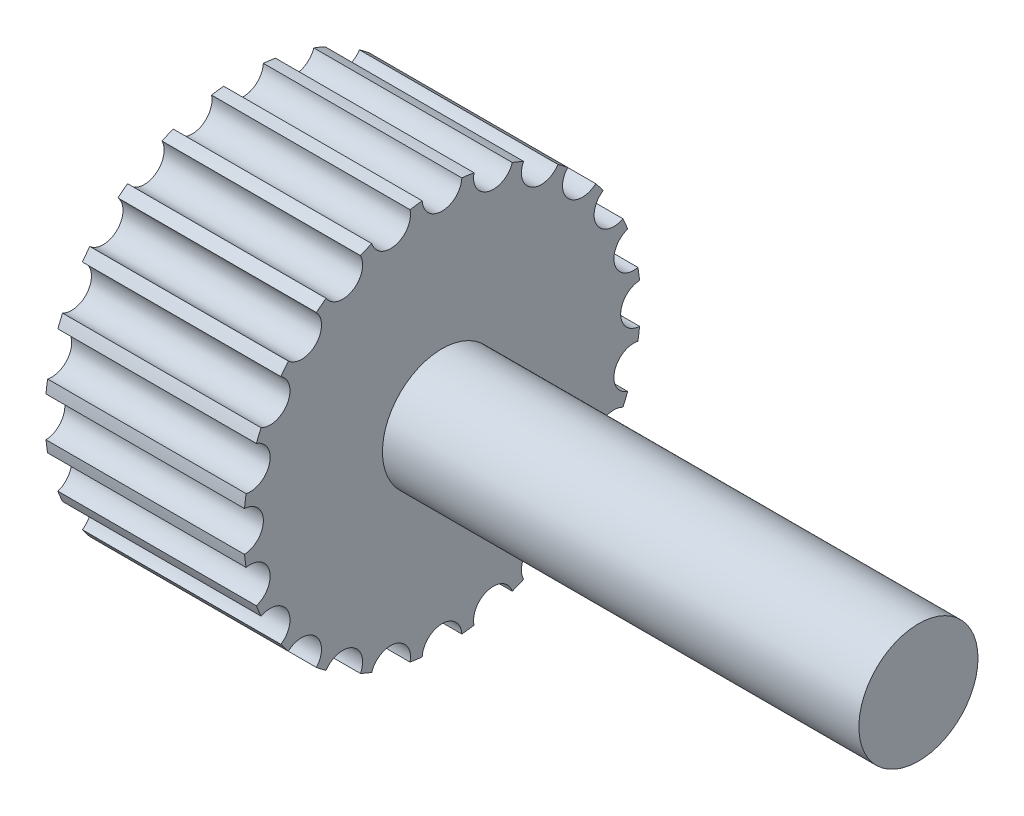
SolidWorks part; units mm, degrees
material "Brass"
ref_plane "Front Plane" through (0, 0, 0) normal (0, 0, 1) x (1, 0, 0)
ref_plane "Top Plane" through (0, 0, 0) normal (0, 1, 0) x (1, 0, 0)
ref_plane "Right Plane" through (0, 0, 0) normal (1, 0, 0) x (0, 0, -1)
sketch "Sketch1" plane through (0, 0, 0) normal (1, 0, 0) x (0, 0, -1)
  circle A0 centre (0, 0) radius 5
  dimension "D1" = 10
extrude "Boss-Extrude1" add sketch "Sketch1" along normal blind 5
sketch "Sketch2" plane through (0, 0, 0) normal (1, 0, 0) x (0, 0, -1)
  circle A0 centre (0, 0) radius 1.5
  dimension "D1" = 3
extrude "Boss-Extrude2" add sketch "Sketch2" along normal blind 17
cosmetic thread "Cosmetic Thread1" parameters "D1"=12, "D2"=0
sketch "Sketch3" plane through (0, 0, 0) normal (1, 0, 0) x (0, 0, -1)
  circle A0 centre (5, 0) radius 0.5
  dimension "D2" = 1
  dimension "D1" = 5
extrude "Cut-Extrude2" cut sketch "Sketch3" against normal blind 5 and the other way blind 5
ref_axis "Axis1" through (-0.85, 0, 0) along (1, 0, 0)
pattern_circular "CirPattern1" count 24 over 360 about axis through (-0.85, 0, 0) along (1, 0, 0) of "Cut-Extrude2"
